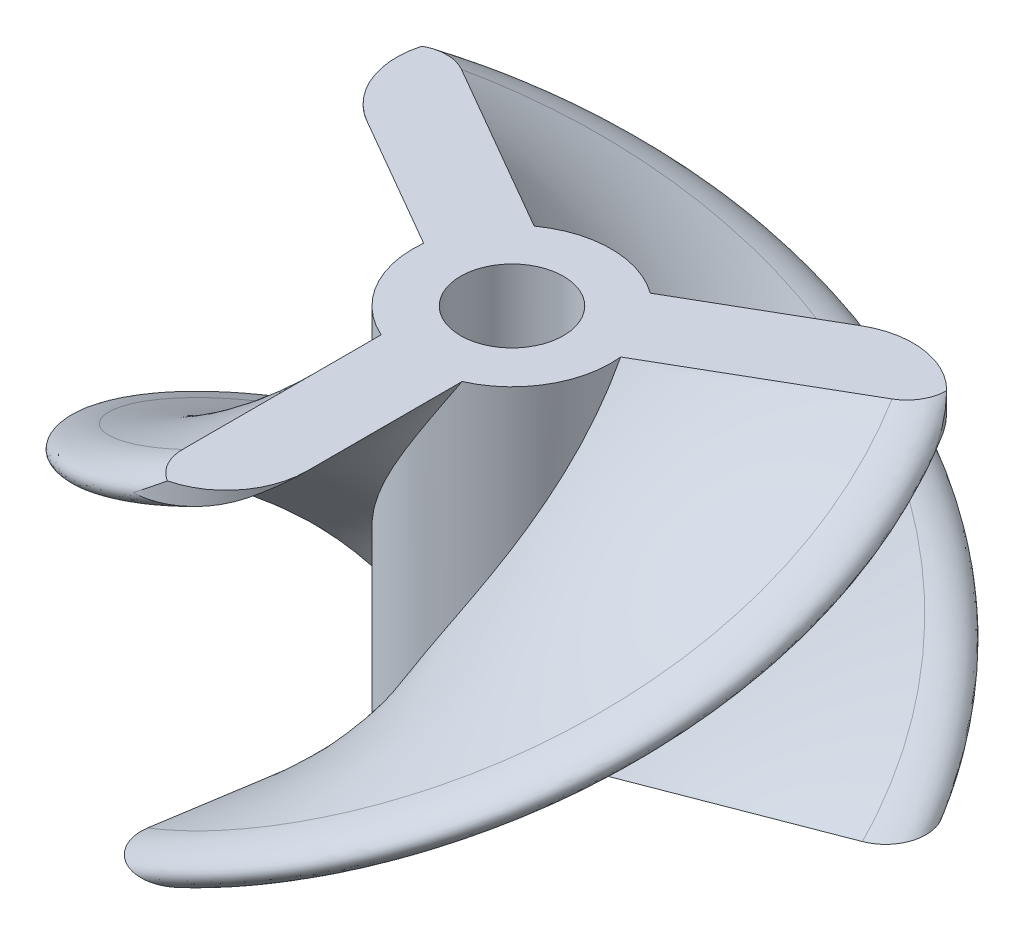
SolidWorks part; units mm, degrees
material "6061-T6 (SS)"
ref_plane "Front Plane" through (0, 0, 0) normal (0, 0, 1) x (1, 0, 0)
ref_plane "Top Plane" through (0, 0, 0) normal (0, 1, 0) x (1, 0, 0)
ref_plane "Right Plane" through (0, 0, 0) normal (1, 0, 0) x (0, 0, -1)
ref_axis "Axis1" through (0, 28.9225, 0) along (0, -1, 0)
sketch "Sketch1" plane through (0, 0, 0) normal (0, 1, 0) x (1, 0, 0)
  circle A0 centre (0, 0) radius 12.9286
  point P3 (0, 0)
  dimension "D1" = 25.8572
curve "Helix/Spiral1" pitch 38.862 height 13.9192 radius 12.9286 centre (0, 0, 0) axis (0, -1, 0) start towards (0, 0, 1)
sketch "Sketch2" plane through (0, 0, 0) normal (0, 1, 0) x (1, 0, 0)
  line L1 (1.5875, 0) -> (-1.5875, 0)
  line L2 (1.5875, 0) -> (1.5875, -11.3411)
  line L4 (-1.5875, 0) -> (-1.5875, -11.3411)
  arc A0 (-1.5875, -11.3411) -> (1.5875, -11.3411) centre (0, -11.3411) ccw
  point P4 (0, -12.9286)
  dimension "D2" = 3.175
  dimension "D1" = 12.9286
sweep "Sweep1" add profiles "Sketch2" path "Helix/Spiral1"
sketch "Sketch4" plane through (0, 0, 0) normal (0, 0, 1) x (1, 0, 0)
  line L0 (0, 0) -> (0, -13.9193)
  line L1 (0, 0) -> (3.8862, 0)
  line L2 (3.8862, 0) -> (3.8862, -13.9193)
  line L3 (0, -13.9193) -> (-4.9832, -13.9193) construction
  line L4 (0, -13.9193) -> (3.8862, -13.9193)
  spline S0 degree 1 poles (0.9977, -13.9192) (-0.9977, -13.9194) knots 0 0 1 1 construction
  dimension "D1" = 3.8862
revolve "Revolve1" add sketch "Sketch4" angle 360 about L0
sketch "Sketch10" plane through (0, 0, 0) normal (0, 1, 0) x (1, 0, 0)
  line L0 (-2.1043, -12.7562) -> (-14.8262, -10.6576)
  line L1 (-1.5875, -9.6235) -> (-2.1043, -12.7562) construction
  line L2 (1.5875, -9.6235) -> (1.5875, -12.8308)
  line L3 (1.5875, -11.3411) -> (1.5875, -3.5472) construction
  line L4 (1.5875, -9.6235) -> (-1.5875, -9.6235) construction
  line L5 (-1.5875, -3.5472) -> (-1.5875, -11.3411) construction
  arc A0 (1.5875, -9.6235) -> (-2.1043, -12.7562) centre (-1.5875, -9.6235) cw
  circle A2 centre (0, 0) radius 12.9286
  arc A5 (-1.5875, -11.3411) -> (1.5875, -11.3411) centre (0, -11.3411) ccw construction
  point P11 (0, -9.7536)
  spline M4 degree 1 poles (1.5875, -11.3411) (1.5875, 0) knots 0 0 1 1 weights 1 1 only from (1.5875, -11.3411) to (1.5875, -3.5472)
  spline M7 degree 3 poles (-1.5875, -11.3411) (-1.5875, -14.5161) (1.5875, -14.5161) (1.5875, -11.3411) knots 0 0 0 0 1 1 1 1 weights 1 0.333333 0.333333 1
  dimension "D1" = 25.8572
extrude "Cut-Extrude1" cut sketch "Sketch10" against normal up to next contours A0 M4 M7 | A0 A2 M7 | A2 L2 M7 region at (0.7644, 0, 12.0447) region at (1.2373, 0, 12.5396) region at (-0.9395, 0, 12.8306)
pattern_circular "CirPattern1" count 3 over 360 about axis through (0, 28.9225, 0) along (0, -1, 0) of "Sweep1", "Cut-Extrude1"
hole_wizard "Tap Drill for #10-32 Tap1" positions "3DSketch2" profile "Sketch9" hole size "#10-32" standard "ANSI Inch" end condition through all
sketch3d "3DSketch2"
  point P0 (0, 0, 0)
sketch "Sketch9" plane through (0, 0, 0) normal (1, 0, 0) x (0, 0, 1)
  line L0 (0, 0) -> (0, 13.9799)
  line L1 (0, 13.9799) -> (2.0193, 13.9799)
  line L2 (2.0193, 13.9799) -> (2.0193, 0)
  line L5 (2.0193, 0) -> (0, 0)
  line L11 (0, -6.35) -> (0, 107.95) construction
  dimension "Thru Hole Dia." = 4.0386
  dimension "Thru Hole Depth" = 13.9799
equation "\"Minimum Height\" = .75"
equation "\"Tip Radius\"= .509"
equation "\"Hub Radius\"= .153"
equation "\"Blade Lead\"= 1.53"
equation "\"Axial Clearance\"= .509"
equation "\"D1@Sketch1\"=2*\"Tip Radius\""
equation "\"D1@Sketch4\"=\"Hub Radius\""
equation "\"D1@Sketch2\"=\"Tip Radius\""
equation "\"D1@Sketch10\"=2*\"Tip Radius\""
